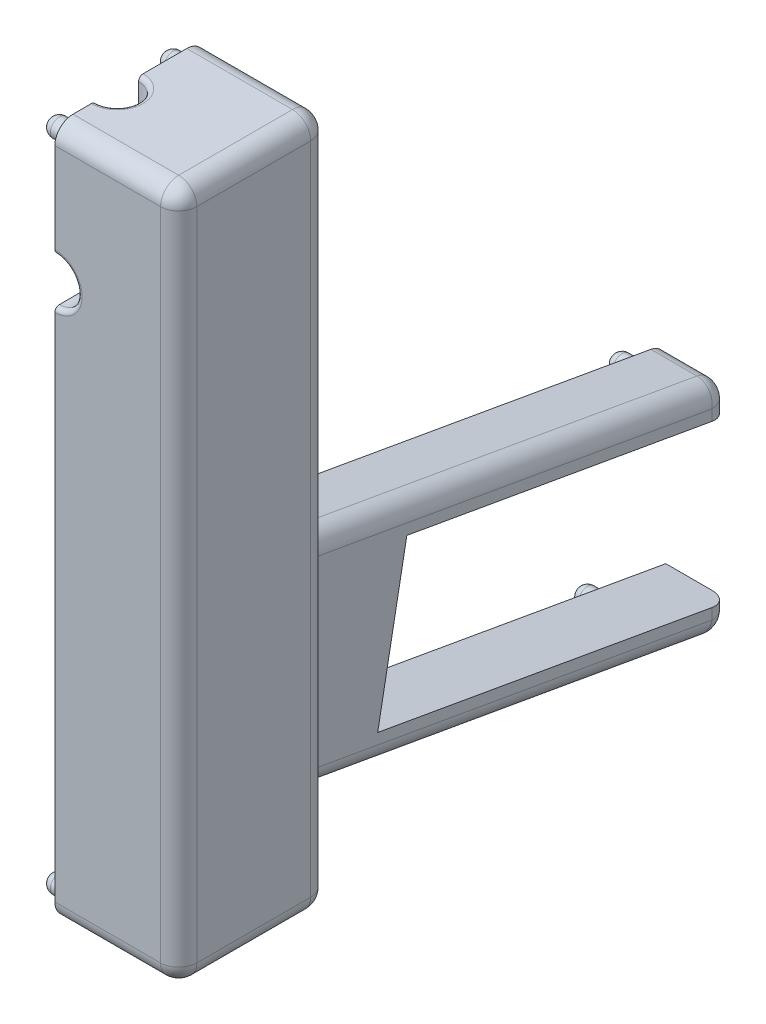
SolidWorks part; units mm, degrees
ref_plane "Front Plane" through (0, 0, 0) normal (0, 0, 1) x (1, 0, 0)
ref_plane "Top Plane" through (0, 0, 0) normal (0, 1, 0) x (1, 0, 0)
ref_plane "Right Plane" through (0, 0, 0) normal (1, 0, 0) x (0, 0, -1)
sketch "Sketch1" plane through (0, 0, 0) normal (0, 1, 0) x (1, 0, 0)
  line L1 (0, 0) -> (27.305, 0)
  line L2 (0, 0) -> (0, 33.1)
  line L3 (0, 33.1) -> (27.305, 33.1)
  line L4 (27.305, 0) -> (27.305, 33.1)
  dimension "D1" = 27.305
  dimension "D2" = 33.1
extrude "Boss-Extrude1" add sketch "Sketch1" along normal blind 152.4
sketch "Sketch2" plane through (0, 0, 0) normal (-1, 0, 0) x (0, 0, 1)
  line L0 (0, 152.4) -> (0, 0) construction
  line L1 (-6.35, 146.05) -> (-26.75, 146.05)
  line L2 (-6.35, 146.05) -> (-6.35, 6.35)
  line L3 (-6.35, 6.35) -> (-26.75, 6.35)
  line L4 (-26.75, 146.05) -> (-26.75, 6.35)
  line L5 (-33.1, 152.4) -> (0, 152.4) construction
  line L6 (-33.1, 152.4) -> (-33.1, 0) construction
  line L7 (-33.1, 0) -> (0, 0) construction
  dimension "D1" = 6.35
  dimension "D2" = 6.35
  dimension "D3" = 6.35
  dimension "D4" = 6.35
extrude "Cut-Extrude1" cut sketch "Sketch2" against normal blind 19.05
sketch "Sketch3" plane through (0, 0, 0) normal (0, 0, 1) x (1, 0, 0)
  line L0 (0, 152.4) -> (0, 0) construction
  line L1 (0, 127.555) -> (0, 117.555)
  arc A0 (0, 127.555) -> (0, 117.555) centre (0, 122.555) cw
  dimension "D1" = 29.845
extrude "HitLED" cut sketch "Sketch3" against normal up to next
sketch "Sketch6" plane through (19.05, 0, 0) normal (-1, 0, 0) x (0, 0, 1)
  line L0 (-15.7, 107.95) -> (-15.7, 33.02)
  line L1 (-9.35, 107.95) -> (-23.75, 107.95)
  line L2 (-9.35, 107.95) -> (-9.35, 33.02)
  line L3 (-9.35, 33.02) -> (-23.75, 33.02)
  line L4 (-23.75, 107.95) -> (-23.75, 33.02)
  line L5 (-17.4, 33.02) -> (-17.4, 107.95)
  line L7 (-6.35, 146.05) -> (-26.75, 146.05) construction
  line L8 (-26.75, 146.05) -> (-26.75, 6.35) construction
  line M8 (-6.35, 146.05) -> (-26.75, 146.05)
  dimension "D1" = 38.1
  dimension "D2" = 3
  dimension "D3" = 1.7
  dimension "D4" = 6.35
  dimension "D5" = 6.35
  dimension "D6" = 74.93
extrude "PCB" add sketch "Sketch6" along normal blind 6.35 contours L3 L2 L0 M8 | L3 L5 L1 L4 region at (19.05, 70.485, -12.525) region at (19.05, 70.485, -20.575)
sketch "Sketch16" plane through (0, 0, 0) normal (-1, 0, 0) x (0, 0, 1)
  line L1 (-33.1, 152.4) -> (0, 152.4) construction
  line L2 (0, 117.555) -> (0, 0) construction
  line L3 (-33.1, 0) -> (0, 0) construction
  line L5 (-33.1, 152.4) -> (-33.1, 0) construction
  circle A0 centre (-4, 148.4) radius 2
  circle A1 centre (-4, 4) radius 2
  circle A2 centre (-29.1, 148.4) radius 2
  circle A3 centre (-29.1, 4) radius 2
  dimension "D1" = 4
  dimension "D3" = 4
  dimension "D2" = 4
  dimension "D4" = 4
extrude "PressFit" add sketch "Sketch16" along normal blind 5
fillet "Fillet-PressFit" radius 2 4 edges at (-5, 4, -27.1) (-5, 4, -2) (-5, 148.4, -27.1) (-5, 148.4, -2)
sketch "Sketch23" plane through (0, 0, -25.4) normal (-1, 0, 0) x (0, 0, 1)
  line L4 (-7.7, 61.1358) -> (-7.7, 12.7)
  line L5 (-7.7, 12.7) -> (-109.3, -5.2148)
  line L6 (-109.3, -5.2148) -> (-109.3, 43.221)
  line L7 (-109.3, 43.221) -> (-7.7, 61.1358)
  dimension "D1" = 47.7
  dimension "D2" = 12.7
extrude "Butt" add sketch "Sketch23" against normal blind 14.175
sketch "Sketch20" plane through (0, 0, 0) normal (-1, 0, 0) x (0, 0, 1)
  line L0 (-63.4356, 49.3389) -> (-57.0033, 14.9332)
  line L1 (-63.4356, 49.3389) -> (-130.4061, 37.5302)
  line L2 (-57.0033, 14.9332) -> (-123.9738, 3.1245)
  line L6 (-130.4061, 37.5302) -> (-134.7, 36.7731)
  line L10 (-123.9738, 3.1245) -> (-134.7, 1.2331)
  line L11 (-134.7, 1.2331) -> (-134.7, 36.7731)
  dimension "D2" = 35
extrude "BatteryPack" cut sketch "Sketch20" against normal blind 14.175
sketch "Sketch22" plane through (0, 0, 0) normal (-1, 0, 0) x (0, 0, 1)
  line L0 (-63.4356, 49.3389) -> (-134.7, 36.7731) construction
  line L2 (-134.7, 1.2331) -> (-57.0033, 14.9332) construction
  line L4 (-57.0033, 14.9332) -> (-63.4356, 49.3389) construction
  circle A0 centre (-128.067, 41.1666) radius 2
  circle A1 centre (-120.4429, 0.5231) radius 2
  dimension "D1" = 3.175
  dimension "D2" = 3.175
  dimension "D3" = 65.0325
  dimension "D4" = 65.0073
extrude "PressFit - Bottom" add sketch "Sketch22" along normal blind 5
sketch "Sketch25" plane through (0, 146.05, 0) normal (0, -1, 0) x (1, 0, 0)
  line L0 (0, -6.35) -> (0, -26.75) construction
  line L1 (0, -9.05) -> (0, -18.45)
  line L2 (19.05, -26.75) -> (0, -26.75) construction
  arc A0 (0, -9.05) -> (0, -18.45) centre (0, -13.75) cw
  dimension "D1" = 13
extrude "IRLED" cut sketch "Sketch25" against normal up to next
fillet "Fillet - Body" radius 4 17 edges at (14.175, -1.9908, -134.7) (14.175, 39.997, -134.7) (7.0875, 43.221, -134.7) (7.0875, -5.2148, -134.7) (14.175, 52.1784, -83.9) (14.175, 3.7426, -83.9) (7.0875, 12.7, -33.1) (14.175, 36.9179, -33.1) (7.0875, 61.1358, -33.1) (13.6525, 152.4, -33.1) (13.6525, 152.4, 0) (27.305, 152.4, -16.55) (27.305, 76.2, -33.1) (27.305, 0, -16.55) (13.6525, 0, -33.1) (13.6525, 0, 0) (27.305, 76.2, 0)
fillet "Fillet-PressFit-Bottom" radius 2 2 edges at (-5, 0.5231, -118.4429) (-5, 41.1666, -126.067)
fillet "Fillet-LED's" radius 1 2 edges at (4.7, 152.4, -13.75) (5, 122.555, 0)
